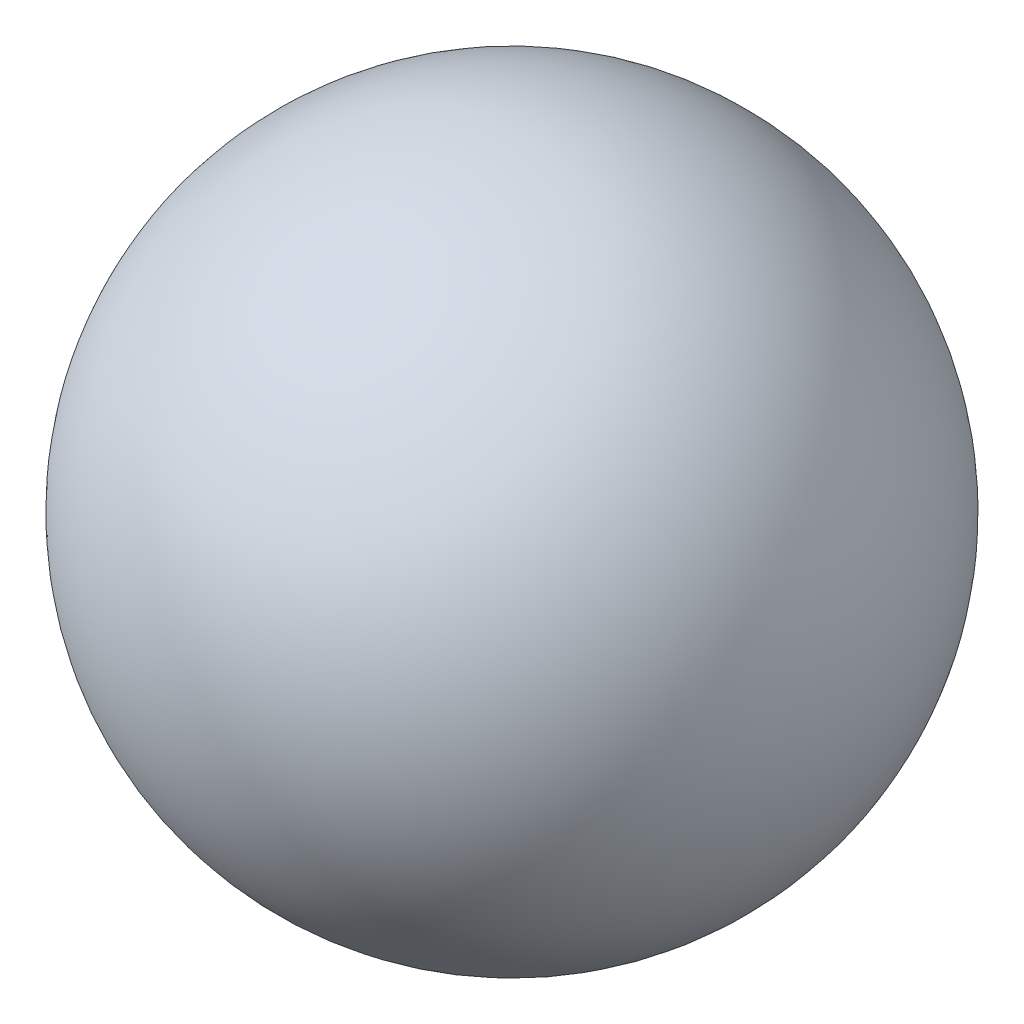
SolidWorks part; units mm, degrees
ref_plane "Front Plane" through (0, 0, 0) normal (0, 0, 1) x (1, 0, 0)
ref_plane "Top Plane" through (0, 0, 0) normal (0, 1, 0) x (1, 0, 0)
ref_plane "Right Plane" through (0, 0, 0) normal (1, 0, 0) x (0, 0, -1)
sketch "Sketch1" plane through (0, 0, 0) normal (0, 0, 1) x (1, 0, 0)
  line L0 (-7.95, 0) -> (7.95, 0)
  circle A0 centre (0, 0) radius 7.95
  dimension "D1" = 15.9
revolve "Revolve1" add sketch "Sketch1" angle 360 about L0 region at (0, 3.3741, 0)
ref_axis "Axis1" through (-7.645, 0, 0) along (1, 0, 0)
